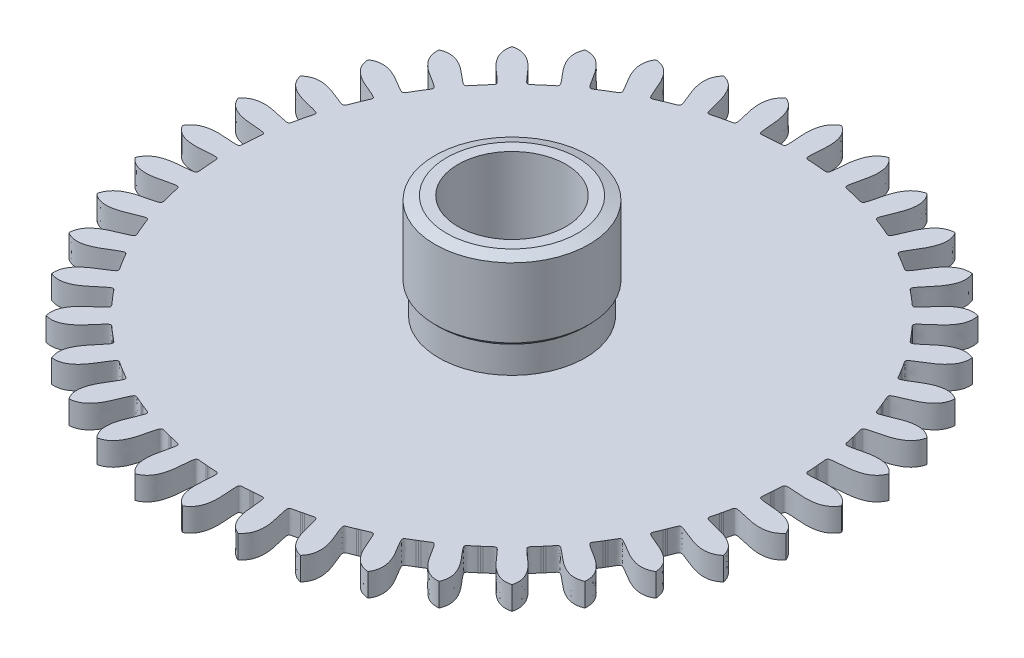
SolidWorks part; units mm, degrees
ref_plane "Alzado" through (0, 0, 0) normal (0, 0, 1) x (1, 0, 0)
ref_plane "Planta" through (0, 0, 0) normal (0, 1, 0) x (1, 0, 0)
ref_plane "Vista lateral" through (0, 0, 0) normal (1, 0, 0) x (0, 0, -1)
sketch "Sketch1" plane through (0, 0, 0) normal (0, 1, 0) x (1, 0, 0)
  line L0 (0, -1000) -> (0, 49000) construction
  line L1 (0, 0) -> (3922.9548, 49845.8667) construction
  line L2 (0.1351, -995.9391) -> (0.1351, 49004.0609) construction
  line L3 (0.2664, 3.6653) -> (0.2883, 3.6637)
  line L4 (-0.2664, 3.6653) -> (-0.2883, 3.6637)
  line L5 (0.3103, 3.6619) -> (0.2883, 3.6637)
  line L6 (0.8365, 3.5785) -> (0.8579, 3.5735)
  line L7 (0.8793, 3.5683) -> (0.8579, 3.5735)
  line L8 (1.386, 3.4036) -> (1.4064, 3.3953)
  line L9 (1.4267, 3.3868) -> (1.4064, 3.3953)
  line L10 (1.9014, 3.1449) -> (1.9202, 3.1335)
  line L11 (1.9389, 3.1219) -> (1.9202, 3.1335)
  line L12 (2.3699, 2.8087) -> (2.3867, 2.7945)
  line L13 (2.4034, 2.7802) -> (2.3867, 2.7945)
  line L14 (2.7802, 2.4034) -> (2.7945, 2.3867)
  line L15 (2.8087, 2.3699) -> (2.7945, 2.3867)
  line L16 (3.1219, 1.9389) -> (3.1335, 1.9202)
  line L17 (3.1449, 1.9014) -> (3.1335, 1.9202)
  line L18 (3.3868, 1.4267) -> (3.3953, 1.4064)
  line L19 (3.4036, 1.386) -> (3.3953, 1.4064)
  line L20 (3.5683, 0.8793) -> (3.5735, 0.8579)
  line L21 (3.5785, 0.8365) -> (3.5735, 0.8579)
  line L22 (3.6619, 0.3103) -> (3.6637, 0.2883)
  line L23 (3.6653, 0.2664) -> (3.6637, 0.2883)
  line L24 (3.6653, -0.2664) -> (3.6637, -0.2883)
  line L25 (3.6619, -0.3103) -> (3.6637, -0.2883)
  line L26 (3.5785, -0.8365) -> (3.5735, -0.8579)
  line L27 (3.5683, -0.8793) -> (3.5735, -0.8579)
  line L28 (3.4036, -1.386) -> (3.3953, -1.4064)
  line L29 (3.3868, -1.4267) -> (3.3953, -1.4064)
  line L30 (3.1449, -1.9014) -> (3.1335, -1.9202)
  line L31 (3.1219, -1.9389) -> (3.1335, -1.9202)
  line L32 (2.8087, -2.3699) -> (2.7945, -2.3867)
  line L33 (2.7802, -2.4034) -> (2.7945, -2.3867)
  line L34 (2.4034, -2.7802) -> (2.3867, -2.7945)
  line L35 (2.3699, -2.8087) -> (2.3867, -2.7945)
  line L36 (1.9389, -3.1219) -> (1.9202, -3.1335)
  line L37 (1.9014, -3.1449) -> (1.9202, -3.1335)
  line L38 (1.4267, -3.3868) -> (1.4064, -3.3953)
  line L39 (1.386, -3.4036) -> (1.4064, -3.3953)
  line L40 (0.8793, -3.5683) -> (0.8579, -3.5735)
  line L41 (0.8365, -3.5785) -> (0.8579, -3.5735)
  line L42 (0.3103, -3.6619) -> (0.2883, -3.6637)
  line L43 (0.2664, -3.6653) -> (0.2883, -3.6637)
  line L44 (-0.2664, -3.6653) -> (-0.2883, -3.6637)
  line L45 (-0.3103, -3.6619) -> (-0.2883, -3.6637)
  line L46 (-0.8365, -3.5785) -> (-0.8579, -3.5735)
  line L47 (-0.8793, -3.5683) -> (-0.8579, -3.5735)
  line L48 (-1.386, -3.4036) -> (-1.4064, -3.3953)
  line L49 (-1.4267, -3.3868) -> (-1.4064, -3.3953)
  line L50 (-1.9014, -3.1449) -> (-1.9202, -3.1335)
  line L51 (-1.9389, -3.1219) -> (-1.9202, -3.1335)
  line L52 (-2.3699, -2.8087) -> (-2.3867, -2.7945)
  line L53 (-2.4034, -2.7802) -> (-2.3867, -2.7945)
  line L54 (-2.7802, -2.4034) -> (-2.7945, -2.3867)
  line L55 (-2.8087, -2.3699) -> (-2.7945, -2.3867)
  line L56 (-3.1219, -1.9389) -> (-3.1335, -1.9202)
  line L57 (-3.1449, -1.9014) -> (-3.1335, -1.9202)
  line L58 (-3.3868, -1.4267) -> (-3.3953, -1.4064)
  line L59 (-3.4036, -1.386) -> (-3.3953, -1.4064)
  line L60 (-3.5683, -0.8793) -> (-3.5735, -0.8579)
  line L61 (-3.5785, -0.8365) -> (-3.5735, -0.8579)
  line L62 (-3.6619, -0.3103) -> (-3.6637, -0.2883)
  line L63 (-3.6653, -0.2664) -> (-3.6637, -0.2883)
  line L64 (-3.6653, 0.2664) -> (-3.6637, 0.2883)
  line L65 (-3.6619, 0.3103) -> (-3.6637, 0.2883)
  line L66 (-3.5785, 0.8365) -> (-3.5735, 0.8579)
  line L67 (-3.5683, 0.8793) -> (-3.5735, 0.8579)
  line L68 (-3.4036, 1.386) -> (-3.3953, 1.4064)
  line L69 (-3.3868, 1.4267) -> (-3.3953, 1.4064)
  line L70 (-3.1449, 1.9014) -> (-3.1335, 1.9202)
  line L71 (-3.1219, 1.9389) -> (-3.1335, 1.9202)
  line L72 (-2.8087, 2.3699) -> (-2.7945, 2.3867)
  line L73 (-2.7802, 2.4034) -> (-2.7945, 2.3867)
  line L74 (-2.4034, 2.7802) -> (-2.3867, 2.7945)
  line L75 (-2.3699, 2.8087) -> (-2.3867, 2.7945)
  line L76 (-1.9389, 3.1219) -> (-1.9202, 3.1335)
  line L77 (-1.9014, 3.1449) -> (-1.9202, 3.1335)
  line L78 (-1.4267, 3.3868) -> (-1.4064, 3.3953)
  line L79 (-1.386, 3.4036) -> (-1.4064, 3.3953)
  line L80 (-0.8793, 3.5683) -> (-0.8579, 3.5735)
  line L81 (-0.8365, 3.5785) -> (-0.8579, 3.5735)
  line L82 (-0.3103, 3.6619) -> (-0.2883, 3.6637)
  circle A0 centre (0, 0) radius 4.275 construction
  circle A1 centre (0, 0) radius 3.675 construction
  spline S0 degree 3 poles (0, 4.275) (0.0808, 4.2262) (0.1721, 4.1272) (0.137, 3.8054) (0.1357, 3.7597) (0.132, 3.6514) (0.1617, 3.6778) (0.2664, 3.6653) knots 0 0 0 0 0.596043 0.670236 0.733963 0.767736 1 1 1 1
  spline S1 degree 3 poles (0, 4.275) (-0.0808, 4.2262) (-0.1721, 4.1272) (-0.137, 3.8054) (-0.1357, 3.7597) (-0.132, 3.6514) (-0.1617, 3.6778) (-0.2664, 3.6653) knots 0 0 0 0 0.596043 0.670236 0.733963 0.767736 1 1 1 1
  spline S2 degree 3 poles (0.6688, 4.2224) (0.5814, 4.1868) (0.4756, 4.1033) (0.4599, 3.78) (0.4541, 3.7346) (0.4408, 3.627) (0.4156, 3.6578) (0.3103, 3.6619) knots 0 0 0 0 0.596043 0.670236 0.733963 0.767736 1 1 1 1
  spline S3 degree 3 poles (0.6688, 4.2224) (0.7409, 4.1616) (0.8156, 4.0495) (0.7306, 3.7371) (0.7222, 3.6922) (0.7016, 3.5857) (0.7351, 3.6072) (0.8365, 3.5785) knots 0 0 0 0 0.596043 0.670236 0.733963 0.767736 1 1 1 1
  spline S4 degree 3 poles (1.321, 4.0658) (1.2292, 4.0443) (1.1117, 3.9784) (1.0456, 3.6615) (1.0327, 3.6176) (1.0028, 3.5134) (0.9827, 3.5477) (0.8793, 3.5683) knots 0 0 0 0 0.596043 0.670236 0.733963 0.767736 1 1 1 1
  spline S5 degree 3 poles (1.321, 4.0658) (1.3828, 3.9944) (1.4391, 3.872) (1.3063, 3.5768) (1.2909, 3.5337) (1.2539, 3.4319) (1.2903, 3.4478) (1.386, 3.4036) knots 0 0 0 0 0.596043 0.670236 0.733963 0.767736 1 1 1 1
  spline S6 degree 3 poles (1.9408, 3.8091) (1.8467, 3.8023) (1.7203, 3.7555) (1.6055, 3.4528) (1.5859, 3.4115) (1.5401, 3.3133) (1.5256, 3.3503) (1.4267, 3.3868) knots 0 0 0 0 0.596043 0.670236 0.733963 0.767736 1 1 1 1
  spline S7 degree 3 poles (1.9408, 3.8091) (1.9906, 3.7289) (2.0271, 3.5992) (1.8497, 3.3284) (1.8278, 3.2883) (1.7753, 3.1935) (1.8138, 3.2035) (1.9014, 3.1449) knots 0 0 0 0 0.596043 0.670236 0.733963 0.767736 1 1 1 1
  spline S8 degree 3 poles (2.5128, 3.4585) (2.4188, 3.4666) (2.2867, 3.4401) (2.1259, 3.1592) (2.1001, 3.1214) (2.0394, 3.0316) (2.0309, 3.0704) (1.9389, 3.1219) knots 0 0 0 0 0.596043 0.670236 0.733963 0.767736 1 1 1 1
  spline S9 degree 3 poles (2.5128, 3.4585) (2.5494, 3.3716) (2.5651, 3.2378) (2.3476, 2.9981) (2.3197, 2.9619) (2.253, 2.8764) (2.2926, 2.8803) (2.3699, 2.8087) knots 0 0 0 0 0.596043 0.670236 0.733963 0.767736 1 1 1 1
  spline S10 degree 3 poles (3.0229, 3.0229) (2.9313, 3.0455) (2.7967, 3.0401) (2.5939, 2.7877) (2.5625, 2.7545) (2.4886, 2.6752) (2.4862, 2.7149) (2.4034, 2.7802) knots 0 0 0 0 0.596043 0.670236 0.733963 0.767736 1 1 1 1
  spline S11 degree 3 poles (3.0229, 3.0229) (3.0455, 2.9313) (3.0401, 2.7967) (2.7877, 2.5939) (2.7545, 2.5625) (2.6752, 2.4886) (2.7149, 2.4862) (2.7802, 2.4034) knots 0 0 0 0 0.596043 0.670236 0.733963 0.767736 1 1 1 1
  spline S12 degree 3 poles (3.4585, 2.5128) (3.3716, 2.5494) (3.2378, 2.5651) (2.9981, 2.3476) (2.9619, 2.3197) (2.8764, 2.253) (2.8803, 2.2926) (2.8087, 2.3699) knots 0 0 0 0 0.596043 0.670236 0.733963 0.767736 1 1 1 1
  spline S13 degree 3 poles (3.4585, 2.5128) (3.4666, 2.4188) (3.4401, 2.2867) (3.1592, 2.1259) (3.1214, 2.1001) (3.0316, 2.0394) (3.0704, 2.0309) (3.1219, 1.9389) knots 0 0 0 0 0.596043 0.670236 0.733963 0.767736 1 1 1 1
  spline S14 degree 3 poles (3.8091, 1.9408) (3.7289, 1.9906) (3.5992, 2.0271) (3.3284, 1.8497) (3.2883, 1.8278) (3.1935, 1.7753) (3.2035, 1.8138) (3.1449, 1.9014) knots 0 0 0 0 0.596043 0.670236 0.733963 0.767736 1 1 1 1
  spline S15 degree 3 poles (3.8091, 1.9408) (3.8023, 1.8467) (3.7555, 1.7203) (3.4528, 1.6055) (3.4115, 1.5859) (3.3133, 1.5401) (3.3503, 1.5256) (3.3868, 1.4267) knots 0 0 0 0 0.596043 0.670236 0.733963 0.767736 1 1 1 1
  spline S16 degree 3 poles (4.0658, 1.321) (3.9944, 1.3828) (3.872, 1.4391) (3.5768, 1.3063) (3.5337, 1.2909) (3.4319, 1.2539) (3.4478, 1.2903) (3.4036, 1.386) knots 0 0 0 0 0.596043 0.670236 0.733963 0.767736 1 1 1 1
  spline S17 degree 3 poles (4.0658, 1.321) (4.0443, 1.2292) (3.9784, 1.1117) (3.6615, 1.0456) (3.6176, 1.0327) (3.5134, 1.0028) (3.5477, 0.9827) (3.5683, 0.8793) knots 0 0 0 0 0.596043 0.670236 0.733963 0.767736 1 1 1 1
  spline S18 degree 3 poles (4.2224, 0.6688) (4.1616, 0.7409) (4.0495, 0.8156) (3.7371, 0.7306) (3.6922, 0.7222) (3.5857, 0.7016) (3.6072, 0.7351) (3.5785, 0.8365) knots 0 0 0 0 0.596043 0.670236 0.733963 0.767736 1 1 1 1
  spline S19 degree 3 poles (4.2224, 0.6688) (4.1868, 0.5814) (4.1033, 0.4756) (3.78, 0.4599) (3.7346, 0.4541) (3.627, 0.4408) (3.6578, 0.4156) (3.6619, 0.3103) knots 0 0 0 0 0.596043 0.670236 0.733963 0.767736 1 1 1 1
  spline S20 degree 3 poles (4.275, 0) (4.2262, 0.0808) (4.1272, 0.1721) (3.8054, 0.137) (3.7597, 0.1357) (3.6514, 0.132) (3.6778, 0.1617) (3.6653, 0.2664) knots 0 0 0 0 0.596043 0.670236 0.733963 0.767736 1 1 1 1
  spline S21 degree 3 poles (4.275, 0) (4.2262, -0.0808) (4.1272, -0.1721) (3.8054, -0.137) (3.7597, -0.1357) (3.6514, -0.132) (3.6778, -0.1617) (3.6653, -0.2664) knots 0 0 0 0 0.596043 0.670236 0.733963 0.767736 1 1 1 1
  spline S22 degree 3 poles (4.2224, -0.6688) (4.1868, -0.5814) (4.1033, -0.4756) (3.78, -0.4599) (3.7346, -0.4541) (3.627, -0.4408) (3.6578, -0.4156) (3.6619, -0.3103) knots 0 0 0 0 0.596043 0.670236 0.733963 0.767736 1 1 1 1
  spline S23 degree 3 poles (4.2224, -0.6688) (4.1616, -0.7409) (4.0495, -0.8156) (3.7371, -0.7306) (3.6922, -0.7222) (3.5857, -0.7016) (3.6072, -0.7351) (3.5785, -0.8365) knots 0 0 0 0 0.596043 0.670236 0.733963 0.767736 1 1 1 1
  spline S24 degree 3 poles (4.0658, -1.321) (4.0443, -1.2292) (3.9784, -1.1117) (3.6615, -1.0456) (3.6176, -1.0327) (3.5134, -1.0028) (3.5477, -0.9827) (3.5683, -0.8793) knots 0 0 0 0 0.596043 0.670236 0.733963 0.767736 1 1 1 1
  spline S25 degree 3 poles (4.0658, -1.321) (3.9944, -1.3828) (3.872, -1.4391) (3.5768, -1.3063) (3.5337, -1.2909) (3.4319, -1.2539) (3.4478, -1.2903) (3.4036, -1.386) knots 0 0 0 0 0.596043 0.670236 0.733963 0.767736 1 1 1 1
  spline S26 degree 3 poles (3.8091, -1.9408) (3.8023, -1.8467) (3.7555, -1.7203) (3.4528, -1.6055) (3.4115, -1.5859) (3.3133, -1.5401) (3.3503, -1.5256) (3.3868, -1.4267) knots 0 0 0 0 0.596043 0.670236 0.733963 0.767736 1 1 1 1
  spline S27 degree 3 poles (3.8091, -1.9408) (3.7289, -1.9906) (3.5992, -2.0271) (3.3284, -1.8497) (3.2883, -1.8278) (3.1935, -1.7753) (3.2035, -1.8138) (3.1449, -1.9014) knots 0 0 0 0 0.596043 0.670236 0.733963 0.767736 1 1 1 1
  spline S28 degree 3 poles (3.4585, -2.5128) (3.4666, -2.4188) (3.4401, -2.2867) (3.1592, -2.1259) (3.1214, -2.1001) (3.0316, -2.0394) (3.0704, -2.0309) (3.1219, -1.9389) knots 0 0 0 0 0.596043 0.670236 0.733963 0.767736 1 1 1 1
  spline S29 degree 3 poles (3.4585, -2.5128) (3.3716, -2.5494) (3.2378, -2.5651) (2.9981, -2.3476) (2.9619, -2.3197) (2.8764, -2.253) (2.8803, -2.2926) (2.8087, -2.3699) knots 0 0 0 0 0.596043 0.670236 0.733963 0.767736 1 1 1 1
  spline S30 degree 3 poles (3.0229, -3.0229) (3.0455, -2.9313) (3.0401, -2.7967) (2.7877, -2.5939) (2.7545, -2.5625) (2.6752, -2.4886) (2.7149, -2.4862) (2.7802, -2.4034) knots 0 0 0 0 0.596043 0.670236 0.733963 0.767736 1 1 1 1
  spline S31 degree 3 poles (3.0229, -3.0229) (2.9313, -3.0455) (2.7967, -3.0401) (2.5939, -2.7877) (2.5625, -2.7545) (2.4886, -2.6752) (2.4862, -2.7149) (2.4034, -2.7802) knots 0 0 0 0 0.596043 0.670236 0.733963 0.767736 1 1 1 1
  spline S32 degree 3 poles (2.5128, -3.4585) (2.5494, -3.3716) (2.5651, -3.2378) (2.3476, -2.9981) (2.3197, -2.9619) (2.253, -2.8764) (2.2926, -2.8803) (2.3699, -2.8087) knots 0 0 0 0 0.596043 0.670236 0.733963 0.767736 1 1 1 1
  spline S33 degree 3 poles (2.5128, -3.4585) (2.4188, -3.4666) (2.2867, -3.4401) (2.1259, -3.1592) (2.1001, -3.1214) (2.0394, -3.0316) (2.0309, -3.0704) (1.9389, -3.1219) knots 0 0 0 0 0.596043 0.670236 0.733963 0.767736 1 1 1 1
  spline S34 degree 3 poles (1.9408, -3.8091) (1.9906, -3.7289) (2.0271, -3.5992) (1.8497, -3.3284) (1.8278, -3.2883) (1.7753, -3.1935) (1.8138, -3.2035) (1.9014, -3.1449) knots 0 0 0 0 0.596043 0.670236 0.733963 0.767736 1 1 1 1
  spline S35 degree 3 poles (1.9408, -3.8091) (1.8467, -3.8023) (1.7203, -3.7555) (1.6055, -3.4528) (1.5859, -3.4115) (1.5401, -3.3133) (1.5256, -3.3503) (1.4267, -3.3868) knots 0 0 0 0 0.596043 0.670236 0.733963 0.767736 1 1 1 1
  spline S36 degree 3 poles (1.321, -4.0658) (1.3828, -3.9944) (1.4391, -3.872) (1.3063, -3.5768) (1.2909, -3.5337) (1.2539, -3.4319) (1.2903, -3.4478) (1.386, -3.4036) knots 0 0 0 0 0.596043 0.670236 0.733963 0.767736 1 1 1 1
  spline S37 degree 3 poles (1.321, -4.0658) (1.2292, -4.0443) (1.1117, -3.9784) (1.0456, -3.6615) (1.0327, -3.6176) (1.0028, -3.5134) (0.9827, -3.5477) (0.8793, -3.5683) knots 0 0 0 0 0.596043 0.670236 0.733963 0.767736 1 1 1 1
  spline S38 degree 3 poles (0.6688, -4.2224) (0.7409, -4.1616) (0.8156, -4.0495) (0.7306, -3.7371) (0.7222, -3.6922) (0.7016, -3.5857) (0.7351, -3.6072) (0.8365, -3.5785) knots 0 0 0 0 0.596043 0.670236 0.733963 0.767736 1 1 1 1
  spline S39 degree 3 poles (0.6688, -4.2224) (0.5814, -4.1868) (0.4756, -4.1033) (0.4599, -3.78) (0.4541, -3.7346) (0.4408, -3.627) (0.4156, -3.6578) (0.3103, -3.6619) knots 0 0 0 0 0.596043 0.670236 0.733963 0.767736 1 1 1 1
  spline S40 degree 3 poles (0, -4.275) (0.0808, -4.2262) (0.1721, -4.1272) (0.137, -3.8054) (0.1357, -3.7597) (0.132, -3.6514) (0.1617, -3.6778) (0.2664, -3.6653) knots 0 0 0 0 0.596043 0.670236 0.733963 0.767736 1 1 1 1
  spline S41 degree 3 poles (0, -4.275) (-0.0808, -4.2262) (-0.1721, -4.1272) (-0.137, -3.8054) (-0.1357, -3.7597) (-0.132, -3.6514) (-0.1617, -3.6778) (-0.2664, -3.6653) knots 0 0 0 0 0.596043 0.670236 0.733963 0.767736 1 1 1 1
  spline S42 degree 3 poles (-0.6688, -4.2224) (-0.5814, -4.1868) (-0.4756, -4.1033) (-0.4599, -3.78) (-0.4541, -3.7346) (-0.4408, -3.627) (-0.4156, -3.6578) (-0.3103, -3.6619) knots 0 0 0 0 0.596043 0.670236 0.733963 0.767736 1 1 1 1
  spline S43 degree 3 poles (-0.6688, -4.2224) (-0.7409, -4.1616) (-0.8156, -4.0495) (-0.7306, -3.7371) (-0.7222, -3.6922) (-0.7016, -3.5857) (-0.7351, -3.6072) (-0.8365, -3.5785) knots 0 0 0 0 0.596043 0.670236 0.733963 0.767736 1 1 1 1
  spline S44 degree 3 poles (-1.321, -4.0658) (-1.2292, -4.0443) (-1.1117, -3.9784) (-1.0456, -3.6615) (-1.0327, -3.6176) (-1.0028, -3.5134) (-0.9827, -3.5477) (-0.8793, -3.5683) knots 0 0 0 0 0.596043 0.670236 0.733963 0.767736 1 1 1 1
  spline S45 degree 3 poles (-1.321, -4.0658) (-1.3828, -3.9944) (-1.4391, -3.872) (-1.3063, -3.5768) (-1.2909, -3.5337) (-1.2539, -3.4319) (-1.2903, -3.4478) (-1.386, -3.4036) knots 0 0 0 0 0.596043 0.670236 0.733963 0.767736 1 1 1 1
  spline S46 degree 3 poles (-1.9408, -3.8091) (-1.8467, -3.8023) (-1.7203, -3.7555) (-1.6055, -3.4528) (-1.5859, -3.4115) (-1.5401, -3.3133) (-1.5256, -3.3503) (-1.4267, -3.3868) knots 0 0 0 0 0.596043 0.670236 0.733963 0.767736 1 1 1 1
  spline S47 degree 3 poles (-1.9408, -3.8091) (-1.9906, -3.7289) (-2.0271, -3.5992) (-1.8497, -3.3284) (-1.8278, -3.2883) (-1.7753, -3.1935) (-1.8138, -3.2035) (-1.9014, -3.1449) knots 0 0 0 0 0.596043 0.670236 0.733963 0.767736 1 1 1 1
  spline S48 degree 3 poles (-2.5128, -3.4585) (-2.4188, -3.4666) (-2.2867, -3.4401) (-2.1259, -3.1592) (-2.1001, -3.1214) (-2.0394, -3.0316) (-2.0309, -3.0704) (-1.9389, -3.1219) knots 0 0 0 0 0.596043 0.670236 0.733963 0.767736 1 1 1 1
  spline S49 degree 3 poles (-2.5128, -3.4585) (-2.5494, -3.3716) (-2.5651, -3.2378) (-2.3476, -2.9981) (-2.3197, -2.9619) (-2.253, -2.8764) (-2.2926, -2.8803) (-2.3699, -2.8087) knots 0 0 0 0 0.596043 0.670236 0.733963 0.767736 1 1 1 1
  spline S50 degree 3 poles (-3.0229, -3.0229) (-2.9313, -3.0455) (-2.7967, -3.0401) (-2.5939, -2.7877) (-2.5625, -2.7545) (-2.4886, -2.6752) (-2.4862, -2.7149) (-2.4034, -2.7802) knots 0 0 0 0 0.596043 0.670236 0.733963 0.767736 1 1 1 1
  spline S51 degree 3 poles (-3.0229, -3.0229) (-3.0455, -2.9313) (-3.0401, -2.7967) (-2.7877, -2.5939) (-2.7545, -2.5625) (-2.6752, -2.4886) (-2.7149, -2.4862) (-2.7802, -2.4034) knots 0 0 0 0 0.596043 0.670236 0.733963 0.767736 1 1 1 1
  spline S52 degree 3 poles (-3.4585, -2.5128) (-3.3716, -2.5494) (-3.2378, -2.5651) (-2.9981, -2.3476) (-2.9619, -2.3197) (-2.8764, -2.253) (-2.8803, -2.2926) (-2.8087, -2.3699) knots 0 0 0 0 0.596043 0.670236 0.733963 0.767736 1 1 1 1
  spline S53 degree 3 poles (-3.4585, -2.5128) (-3.4666, -2.4188) (-3.4401, -2.2867) (-3.1592, -2.1259) (-3.1214, -2.1001) (-3.0316, -2.0394) (-3.0704, -2.0309) (-3.1219, -1.9389) knots 0 0 0 0 0.596043 0.670236 0.733963 0.767736 1 1 1 1
  spline S54 degree 3 poles (-3.8091, -1.9408) (-3.7289, -1.9906) (-3.5992, -2.0271) (-3.3284, -1.8497) (-3.2883, -1.8278) (-3.1935, -1.7753) (-3.2035, -1.8138) (-3.1449, -1.9014) knots 0 0 0 0 0.596043 0.670236 0.733963 0.767736 1 1 1 1
  spline S55 degree 3 poles (-3.8091, -1.9408) (-3.8023, -1.8467) (-3.7555, -1.7203) (-3.4528, -1.6055) (-3.4115, -1.5859) (-3.3133, -1.5401) (-3.3503, -1.5256) (-3.3868, -1.4267) knots 0 0 0 0 0.596043 0.670236 0.733963 0.767736 1 1 1 1
  spline S56 degree 3 poles (-4.0658, -1.321) (-3.9944, -1.3828) (-3.872, -1.4391) (-3.5768, -1.3063) (-3.5337, -1.2909) (-3.4319, -1.2539) (-3.4478, -1.2903) (-3.4036, -1.386) knots 0 0 0 0 0.596043 0.670236 0.733963 0.767736 1 1 1 1
  spline S57 degree 3 poles (-4.0658, -1.321) (-4.0443, -1.2292) (-3.9784, -1.1117) (-3.6615, -1.0456) (-3.6176, -1.0327) (-3.5134, -1.0028) (-3.5477, -0.9827) (-3.5683, -0.8793) knots 0 0 0 0 0.596043 0.670236 0.733963 0.767736 1 1 1 1
  spline S58 degree 3 poles (-4.2224, -0.6688) (-4.1616, -0.7409) (-4.0495, -0.8156) (-3.7371, -0.7306) (-3.6922, -0.7222) (-3.5857, -0.7016) (-3.6072, -0.7351) (-3.5785, -0.8365) knots 0 0 0 0 0.596043 0.670236 0.733963 0.767736 1 1 1 1
  spline S59 degree 3 poles (-4.2224, -0.6688) (-4.1868, -0.5814) (-4.1033, -0.4756) (-3.78, -0.4599) (-3.7346, -0.4541) (-3.627, -0.4408) (-3.6578, -0.4156) (-3.6619, -0.3103) knots 0 0 0 0 0.596043 0.670236 0.733963 0.767736 1 1 1 1
  spline S60 degree 3 poles (-4.275, 0) (-4.2262, -0.0808) (-4.1272, -0.1721) (-3.8054, -0.137) (-3.7597, -0.1357) (-3.6514, -0.132) (-3.6778, -0.1617) (-3.6653, -0.2664) knots 0 0 0 0 0.596043 0.670236 0.733963 0.767736 1 1 1 1
  spline S61 degree 3 poles (-4.275, 0) (-4.2262, 0.0808) (-4.1272, 0.1721) (-3.8054, 0.137) (-3.7597, 0.1357) (-3.6514, 0.132) (-3.6778, 0.1617) (-3.6653, 0.2664) knots 0 0 0 0 0.596043 0.670236 0.733963 0.767736 1 1 1 1
  spline S62 degree 3 poles (-4.2224, 0.6688) (-4.1868, 0.5814) (-4.1033, 0.4756) (-3.78, 0.4599) (-3.7346, 0.4541) (-3.627, 0.4408) (-3.6578, 0.4156) (-3.6619, 0.3103) knots 0 0 0 0 0.596043 0.670236 0.733963 0.767736 1 1 1 1
  spline S63 degree 3 poles (-4.2224, 0.6688) (-4.1616, 0.7409) (-4.0495, 0.8156) (-3.7371, 0.7306) (-3.6922, 0.7222) (-3.5857, 0.7016) (-3.6072, 0.7351) (-3.5785, 0.8365) knots 0 0 0 0 0.596043 0.670236 0.733963 0.767736 1 1 1 1
  spline S64 degree 3 poles (-4.0658, 1.321) (-4.0443, 1.2292) (-3.9784, 1.1117) (-3.6615, 1.0456) (-3.6176, 1.0327) (-3.5134, 1.0028) (-3.5477, 0.9827) (-3.5683, 0.8793) knots 0 0 0 0 0.596043 0.670236 0.733963 0.767736 1 1 1 1
  spline S65 degree 3 poles (-4.0658, 1.321) (-3.9944, 1.3828) (-3.872, 1.4391) (-3.5768, 1.3063) (-3.5337, 1.2909) (-3.4319, 1.2539) (-3.4478, 1.2903) (-3.4036, 1.386) knots 0 0 0 0 0.596043 0.670236 0.733963 0.767736 1 1 1 1
  spline S66 degree 3 poles (-3.8091, 1.9408) (-3.8023, 1.8467) (-3.7555, 1.7203) (-3.4528, 1.6055) (-3.4115, 1.5859) (-3.3133, 1.5401) (-3.3503, 1.5256) (-3.3868, 1.4267) knots 0 0 0 0 0.596043 0.670236 0.733963 0.767736 1 1 1 1
  spline S67 degree 3 poles (-3.8091, 1.9408) (-3.7289, 1.9906) (-3.5992, 2.0271) (-3.3284, 1.8497) (-3.2883, 1.8278) (-3.1935, 1.7753) (-3.2035, 1.8138) (-3.1449, 1.9014) knots 0 0 0 0 0.596043 0.670236 0.733963 0.767736 1 1 1 1
  spline S68 degree 3 poles (-3.4585, 2.5128) (-3.4666, 2.4188) (-3.4401, 2.2867) (-3.1592, 2.1259) (-3.1214, 2.1001) (-3.0316, 2.0394) (-3.0704, 2.0309) (-3.1219, 1.9389) knots 0 0 0 0 0.596043 0.670236 0.733963 0.767736 1 1 1 1
  spline S69 degree 3 poles (-3.4585, 2.5128) (-3.3716, 2.5494) (-3.2378, 2.5651) (-2.9981, 2.3476) (-2.9619, 2.3197) (-2.8764, 2.253) (-2.8803, 2.2926) (-2.8087, 2.3699) knots 0 0 0 0 0.596043 0.670236 0.733963 0.767736 1 1 1 1
  spline S70 degree 3 poles (-3.0229, 3.0229) (-3.0455, 2.9313) (-3.0401, 2.7967) (-2.7877, 2.5939) (-2.7545, 2.5625) (-2.6752, 2.4886) (-2.7149, 2.4862) (-2.7802, 2.4034) knots 0 0 0 0 0.596043 0.670236 0.733963 0.767736 1 1 1 1
  spline S71 degree 3 poles (-3.0229, 3.0229) (-2.9313, 3.0455) (-2.7967, 3.0401) (-2.5939, 2.7877) (-2.5625, 2.7545) (-2.4886, 2.6752) (-2.4862, 2.7149) (-2.4034, 2.7802) knots 0 0 0 0 0.596043 0.670236 0.733963 0.767736 1 1 1 1
  spline S72 degree 3 poles (-2.5128, 3.4585) (-2.5494, 3.3716) (-2.5651, 3.2378) (-2.3476, 2.9981) (-2.3197, 2.9619) (-2.253, 2.8764) (-2.2926, 2.8803) (-2.3699, 2.8087) knots 0 0 0 0 0.596043 0.670236 0.733963 0.767736 1 1 1 1
  spline S73 degree 3 poles (-2.5128, 3.4585) (-2.4188, 3.4666) (-2.2867, 3.4401) (-2.1259, 3.1592) (-2.1001, 3.1214) (-2.0394, 3.0316) (-2.0309, 3.0704) (-1.9389, 3.1219) knots 0 0 0 0 0.596043 0.670236 0.733963 0.767736 1 1 1 1
  spline S74 degree 3 poles (-1.9408, 3.8091) (-1.9906, 3.7289) (-2.0271, 3.5992) (-1.8497, 3.3284) (-1.8278, 3.2883) (-1.7753, 3.1935) (-1.8138, 3.2035) (-1.9014, 3.1449) knots 0 0 0 0 0.596043 0.670236 0.733963 0.767736 1 1 1 1
  spline S75 degree 3 poles (-1.9408, 3.8091) (-1.8467, 3.8023) (-1.7203, 3.7555) (-1.6055, 3.4528) (-1.5859, 3.4115) (-1.5401, 3.3133) (-1.5256, 3.3503) (-1.4267, 3.3868) knots 0 0 0 0 0.596043 0.670236 0.733963 0.767736 1 1 1 1
  spline S76 degree 3 poles (-1.321, 4.0658) (-1.3828, 3.9944) (-1.4391, 3.872) (-1.3063, 3.5768) (-1.2909, 3.5337) (-1.2539, 3.4319) (-1.2903, 3.4478) (-1.386, 3.4036) knots 0 0 0 0 0.596043 0.670236 0.733963 0.767736 1 1 1 1
  spline S77 degree 3 poles (-1.321, 4.0658) (-1.2292, 4.0443) (-1.1117, 3.9784) (-1.0456, 3.6615) (-1.0327, 3.6176) (-1.0028, 3.5134) (-0.9827, 3.5477) (-0.8793, 3.5683) knots 0 0 0 0 0.596043 0.670236 0.733963 0.767736 1 1 1 1
  spline S78 degree 3 poles (-0.6688, 4.2224) (-0.7409, 4.1616) (-0.8156, 4.0495) (-0.7306, 3.7371) (-0.7222, 3.6922) (-0.7016, 3.5857) (-0.7351, 3.6072) (-0.8365, 3.5785) knots 0 0 0 0 0.596043 0.670236 0.733963 0.767736 1 1 1 1
  spline S79 degree 3 poles (-0.6688, 4.2224) (-0.5814, 4.1868) (-0.4756, 4.1033) (-0.4599, 3.78) (-0.4541, 3.7346) (-0.4408, 3.627) (-0.4156, 3.6578) (-0.3103, 3.6619) knots 0 0 0 0 0.596043 0.670236 0.733963 0.767736 1 1 1 1
  point P4 (0, 4.275)
  point P9 (0.2883, 3.6637)
  point P10 (0.2664, 3.6653)
  point P376 (0, 0)
  dimension "D1" = 8.55
  dimension "D2" = 7.35
  dimension "D3" = 4.5
  dimension "D4" = 0.022
  dimension "D5" = 0.1351
  dimension "D6" = 40
extrude "Boss-Extrude1 (40 teeth)" add sketch "Sketch1" along normal blind 0.3
sketch "Sketch2" plane through (0, 0.3, 0) normal (0, 1, 0) x (1, 0, 0)
  circle A0 centre (0, 0) radius 0.95
  dimension "D1" = 1.9
extrude "Boss-Extrude2" add sketch "Sketch2" along normal blind 0.35
sketch "Sketch3" plane through (0, 0.65, 0) normal (0, 1, 0) x (1, 0, 0)
  circle A0 centre (0, 0) radius 1
  dimension "D1" = 2
extrude "Boss-Extrude3" add sketch "Sketch3" along normal blind 1
chamfer "Chamfer1" distance 0.05 angle 45 1 edges at (0, 0.65, 1)
chamfer "Chamfer2" distance 0.05 angle 71.565 1 edges at (0, 1.65, 1) first distance on face at (0, 0.7, 1)
sketch "Sketch4" plane through (0, 0, 0) normal (0, 1, 0) x (1, 0, 0)
  circle A0 centre (0, 0) radius 0.7
  dimension "D1" = 1.4
extrude "Cut-Extrude1" cut sketch "Sketch4" along normal up to next
